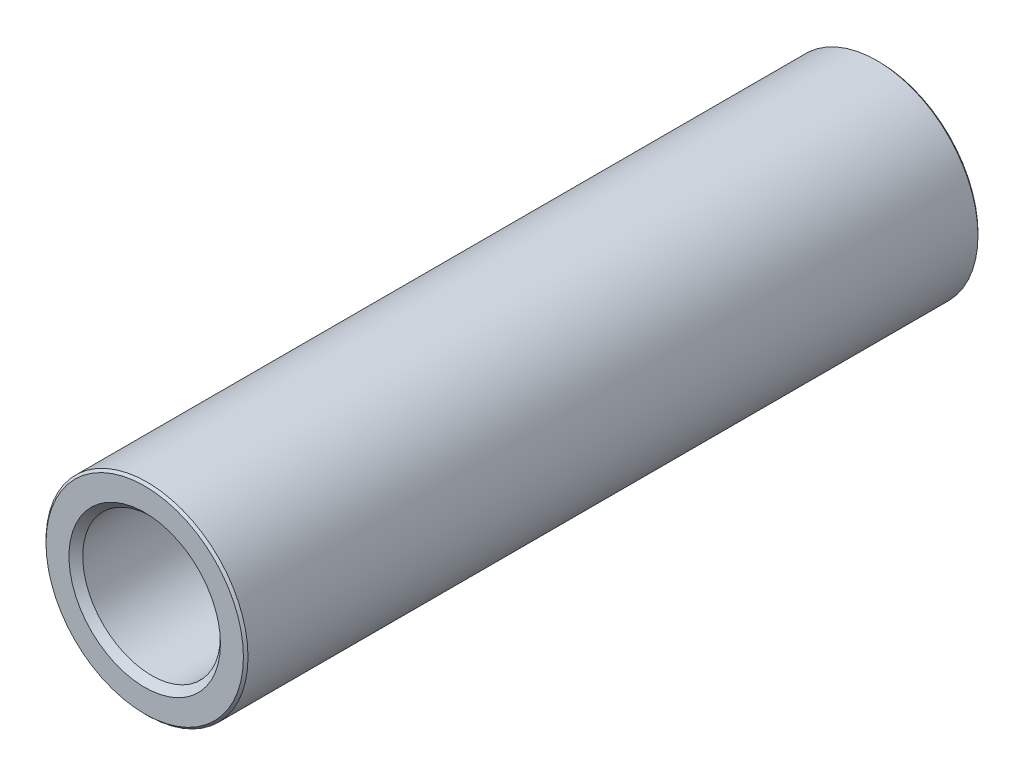
SolidWorks part; units mm, degrees
ref_plane "Front Plane" through (0, 0, 0) normal (0, 0, 1) x (1, 0, 0)
ref_plane "Top Plane" through (0, 0, 0) normal (0, 1, 0) x (1, 0, 0)
ref_plane "Right Plane" through (0, 0, 0) normal (1, 0, 0) x (0, 0, -1)
sketch "Sketch1" plane through (0, 0, 0) normal (0, 0, 1) x (1, 0, 0)
  circle A0 centre (0, 0) radius 11
  circle A1 centre (0, 0) radius 7.5
  dimension "D1" = 22
  dimension "D2" = 15
extrude "Boss-Extrude1" add sketch "Sketch1" along normal blind 40 and the other way blind 40
chamfer "Chamfer1" distance 0.25 angle 45 2 edges at (11, 0, -40) (11, 0, 40)
chamfer "Chamfer2" distance 0.75 angle 45 2 edges at (7.5, 0, 40) (7.5, 0, -40)
